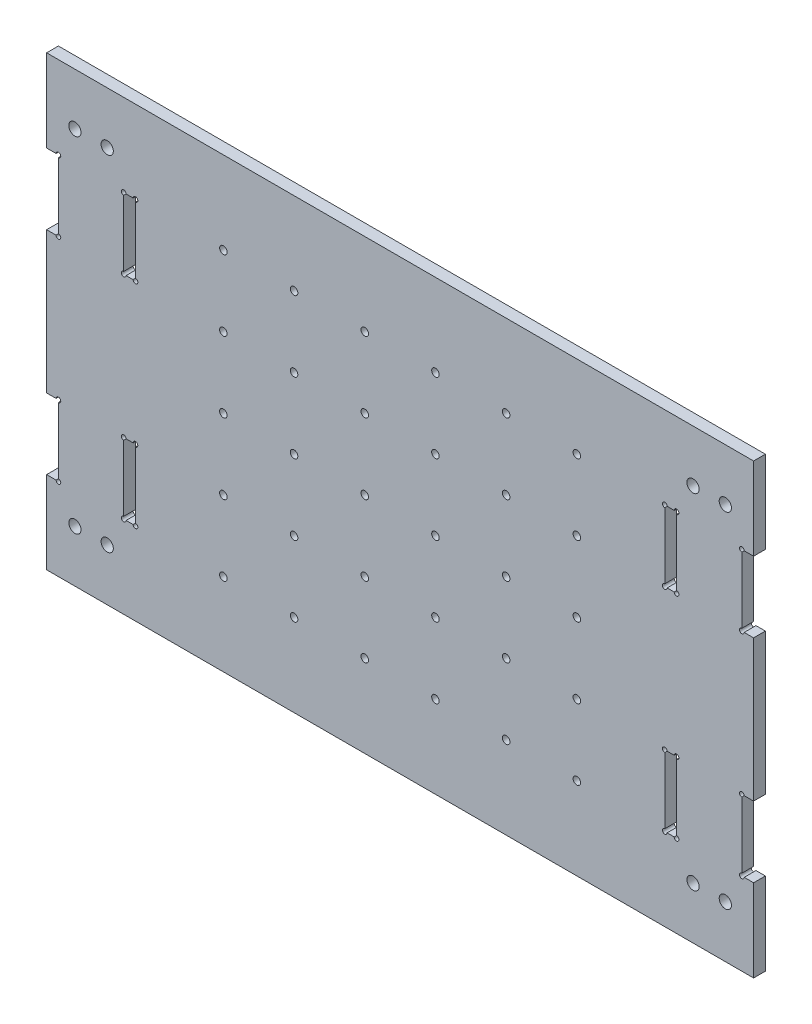
SolidWorks part; units mm, degrees
ref_plane "前视基准面" through (0, 0, 0) normal (0, 0, 1) x (1, 0, 0)
ref_plane "上视基准面" through (0, 0, 0) normal (0, 1, 0) x (1, 0, 0)
ref_plane "右视基准面" through (0, 0, 0) normal (1, 0, 0) x (0, 0, -1)
other "Configuration Table"
sketch "草图1" plane through (0, 0, 0) normal (0, 0, 1) x (1, 0, 0)
  line L0 (0, -95) -> (300, -95) construction
  line L1 (0, 0) -> (300, 0)
  line L2 (0, 0) -> (0, -190)
  line L3 (0, -190) -> (300, -190)
  line L4 (300, 0) -> (300, -190)
  line L5 (50, 0) -> (250, 0)
  line L6 (50, 0) -> (50, -50)
  line L7 (50, -50) -> (250, -50)
  line L8 (250, 0) -> (250, -50)
  line L9 (250, -190) -> (250, -140)
  line L10 (50, -140) -> (250, -140)
  line L11 (50, -190) -> (50, -140)
  dimension "D1" = 300
  dimension "D2" = 190
  dimension "D3" = 50
  dimension "D4" = 50
  dimension "D5" = 50
extrude "凸台-拉伸2" add sketch "草图1" along normal blind 5 contours L2 L0 L4 L1 L8 L7 L6 | L0 L2 L3 L11 L10 L9 L4 region at (150, -59.6622, 0) region at (150, -130.3378, 0)
sketch "草图2" plane through (0, 0, 5) normal (0, 0, 1) x (1, 0, 0)
  line L0 (0, -95) -> (300, -95) construction
  line L1 (150, -50) -> (150, -140) construction
  line L2 (0, -35) -> (5, -35)
  line L3 (0, -35) -> (0, -65)
  line L4 (0, -65) -> (5, -65)
  line L5 (5, -35) -> (5, -65)
  line L6 (0, -155) -> (5, -155)
  line L7 (5, -155) -> (5, -125)
  line L8 (0, -125) -> (5, -125)
  line L9 (300, -155) -> (295, -155)
  line L10 (295, -155) -> (295, -125)
  line L11 (300, -125) -> (295, -125)
  line L12 (0, 0) -> (0, -190)
  line L13 (0, -190) -> (50, -190)
  line L14 (50, -190) -> (50, -140)
  line L15 (50, -140) -> (250, -140)
  line L16 (250, -140) -> (250, -190)
  line L17 (250, -190) -> (300, -190)
  line L18 (300, -190) -> (300, 0)
  line L19 (300, 0) -> (250, 0)
  line L20 (250, 0) -> (250, -50)
  line L21 (250, -50) -> (50, -50)
  line L22 (50, -50) -> (50, 0)
  line L23 (50, 0) -> (0, 0)
  line L24 (0, 0) -> (0, -190)
  line L25 (0, -190) -> (50, -190)
  line L26 (50, -190) -> (50, -140)
  line L27 (50, -140) -> (250, -140)
  line L28 (250, -140) -> (250, -190)
  line L29 (250, -190) -> (300, -190)
  line L30 (300, -190) -> (300, 0)
  line L31 (300, 0) -> (250, 0)
  line L32 (250, 0) -> (250, -50)
  line L33 (250, -50) -> (50, -50)
  line L34 (50, -50) -> (50, 0)
  line L35 (50, 0) -> (0, 0)
  line L36 (300, -65) -> (295, -65)
  line L37 (300, -35) -> (295, -35)
  line L38 (295, -35) -> (295, -65)
  line M22 (0, 0) -> (0, -190)
  line M28 (300, -190) -> (300, 0)
  dimension "D2" = 30
  dimension "D3" = 30
  dimension "D4" = 5
  dimension "D1" = 0
extrude "切除-拉伸1" cut sketch "草图2" against normal blind 10 contours L5 L2 L4 M22 | L8 L6 L7 M22 | L37 L38 L36 L30 | L11 L10 L9 M28 region at (2.5, -50, 5) region at (2.5, -140, 5) region at (297.5, -50, 5) region at (297.5, -140, 5)
sketch "草图3" plane through (0, 0, 5) normal (0, 0, 1) x (1, 0, 0)
  line L0 (150, -50) -> (150, -140) construction
  line L1 (0, -95) -> (300, -95)
  line L28 (0, -65) -> (0, -125)
  line L29 (0, -125) -> (5, -125)
  line L30 (5, -125) -> (5, -155)
  line L31 (5, -155) -> (0, -155)
  line L32 (0, -155) -> (0, -190)
  line L33 (0, -190) -> (50, -190)
  line L34 (50, -190) -> (50, -140)
  line L35 (50, -140) -> (250, -140)
  line L36 (250, -140) -> (250, -190)
  line L37 (250, -190) -> (300, -190)
  line L38 (300, -190) -> (300, -155)
  line L39 (300, -155) -> (295, -155)
  line L40 (295, -155) -> (295, -125)
  line L41 (295, -125) -> (300, -125)
  line L42 (300, -125) -> (300, -65)
  line L43 (300, -65) -> (295, -65)
  line L44 (295, -65) -> (295, -35)
  line L45 (295, -35) -> (300, -35)
  line L46 (300, -35) -> (300, 0)
  line L47 (300, 0) -> (250, 0)
  line L48 (250, 0) -> (250, -50)
  line L49 (250, -50) -> (50, -50)
  line L50 (50, -50) -> (50, 0)
  line L51 (50, 0) -> (0, 0)
  line L52 (0, 0) -> (0, -35)
  line L53 (0, -35) -> (5, -35)
  line L54 (5, -35) -> (5, -65)
  line L55 (5, -65) -> (0, -65)
  line L56 (0, -65) -> (0, -125)
  line L57 (0, -125) -> (5, -125)
  line L58 (5, -125) -> (5, -155)
  line L59 (5, -155) -> (0, -155)
  line L60 (0, -155) -> (0, -190)
  line L61 (0, -190) -> (50, -190)
  line L62 (50, -190) -> (50, -140)
  line L63 (50, -140) -> (250, -140)
  line L64 (250, -140) -> (250, -190)
  line L65 (250, -190) -> (300, -190)
  line L66 (300, -190) -> (300, -155)
  line L67 (300, -155) -> (295, -155)
  line L68 (295, -155) -> (295, -125)
  line L69 (295, -125) -> (300, -125)
  line L70 (300, -125) -> (300, -65)
  line L71 (300, -65) -> (295, -65)
  line L72 (295, -65) -> (295, -35)
  line L73 (295, -35) -> (300, -35)
  line L74 (300, -35) -> (300, 0)
  line L75 (300, 0) -> (250, 0)
  line L76 (250, 0) -> (250, -50)
  line L77 (250, -50) -> (50, -50)
  line L78 (50, -50) -> (50, 0)
  line L79 (50, 0) -> (0, 0)
  line L80 (0, 0) -> (0, -35)
  line L81 (0, -35) -> (5, -35)
  line L82 (5, -35) -> (5, -65)
  line L83 (5, -65) -> (0, -65)
  circle A0 centre (5, -35) radius 1
  circle A1 centre (5, -65) radius 1
  circle A2 centre (5, -125) radius 1
  circle A3 centre (5, -155) radius 1
  circle A4 centre (295, -35) radius 1
  circle A5 centre (295, -65) radius 1
  circle A6 centre (295, -125) radius 1
  circle A7 centre (295, -155) radius 1
  line M31 (5, -125) -> (5, -155)
  line M32 (5, -155) -> (0, -155)
  line M41 (295, -155) -> (295, -125)
  line M42 (295, -125) -> (300, -125)
  line M45 (295, -65) -> (295, -35)
  line M46 (295, -35) -> (300, -35)
  line M55 (5, -35) -> (5, -65)
  line M56 (5, -65) -> (0, -65)
  dimension "D2" = 2
  dimension "D3" = 2
  dimension "D1" = 0
extrude "切除-拉伸2" cut sketch "草图3" against normal blind 10 contours A0 L81 M55 | L81 A0 M55 | A1 M56 M55 | A2 L57 M31 | A3 M31 M32 | A7 L67 M41 | A6 L68 M42 | A4 L72 M46 | A5 L71 M45 region at (5.1415, -65.1415, 5) region at (5.1415, -124.8585, 5) region at (294.8585, -124.8585, 5) region at (294.8585, -65.1415, 5) region at (4.5756, -35.4244, 5) region at (5.1415, -34.8585, 5) region at (5.1415, -155.1415, 5) region at (294.8585, -155.1415, 5) region at (294.8585, -34.8585, 5)
sketch "草图4" plane through (50, 0, 0) normal (1, 0, 0) x (0, 0, -1)
  line L4 (0, -50) -> (0, 0)
  line L5 (0, 0) -> (-5, 0)
  line L6 (-5, 0) -> (-5, -50)
  line L7 (-5, -50) -> (0, -50)
  line L8 (0, -50) -> (0, 0)
  line L9 (0, 0) -> (-5, 0)
  line L10 (-5, 0) -> (-5, -50)
  line L11 (-5, -50) -> (0, -50)
  line L12 (0, -190) -> (0, -140)
  line L13 (0, -140) -> (-5, -140)
  line L14 (-5, -140) -> (-5, -190)
  line L15 (-5, -190) -> (0, -190)
  line L16 (0, -190) -> (0, -140)
  line L17 (0, -140) -> (-5, -140)
  line L18 (-5, -140) -> (-5, -190)
  line L19 (-5, -190) -> (0, -190)
  dimension "D1" = 0
  dimension "D2" = 0
extrude "凸台-拉伸3" add sketch "草图4" along normal up to next
sketch "草图5" plane through (0, 0, 5) normal (0, 0, 1) x (1, 0, 0)
  line L0 (150, 0) -> (150, -190)
  line L1 (32.7, -35) -> (37.7, -35)
  line L2 (32.7, -35) -> (32.7, -65)
  line L3 (32.7, -65) -> (37.7, -65)
  line L4 (37.7, -35) -> (37.7, -65)
  line L5 (0, -95) -> (300, -95)
  line L6 (32.7, -125) -> (37.7, -125)
  line L7 (37.7, -155) -> (37.7, -125)
  line L8 (32.7, -155) -> (37.7, -155)
  line L9 (32.7, -155) -> (32.7, -125)
  line L10 (267.3, -155) -> (267.3, -125)
  line L11 (267.3, -155) -> (262.3, -155)
  line L12 (262.3, -155) -> (262.3, -125)
  line L13 (267.3, -125) -> (262.3, -125)
  line L14 (267.3, -65) -> (262.3, -65)
  line L15 (262.3, -35) -> (262.3, -65)
  line L16 (267.3, -35) -> (262.3, -35)
  line L17 (267.3, -35) -> (267.3, -65)
  line L20 (300, 0) -> (0, 0)
  line L21 (0, 0) -> (0, -35)
  line L22 (0, -35) -> (4, -35)
  line L23 (5, -36) -> (5, -64)
  line L24 (4, -65) -> (0, -65)
  line L25 (0, -65) -> (0, -125)
  line L26 (0, -125) -> (4, -125)
  line L27 (5, -126) -> (5, -154)
  line L28 (4, -155) -> (0, -155)
  line L29 (0, -155) -> (0, -190)
  line L30 (0, -190) -> (300, -190)
  line L31 (300, -190) -> (300, -155)
  line L32 (300, -155) -> (296, -155)
  line L33 (295, -154) -> (295, -126)
  line L34 (296, -125) -> (300, -125)
  line L35 (300, -125) -> (300, -65)
  line L36 (300, -65) -> (296, -65)
  line L37 (295, -64) -> (295, -36)
  line L38 (296, -35) -> (300, -35)
  line L39 (300, -35) -> (300, 0)
  line L40 (300, 0) -> (0, 0)
  line L41 (0, 0) -> (0, -35)
  line L42 (0, -35) -> (4, -35)
  line L43 (5, -36) -> (5, -64)
  line L44 (4, -65) -> (0, -65)
  line L45 (0, -65) -> (0, -125)
  line L46 (0, -125) -> (4, -125)
  line L47 (5, -126) -> (5, -154)
  line L48 (4, -155) -> (0, -155)
  line L49 (0, -155) -> (0, -190)
  line L50 (0, -190) -> (300, -190)
  line L51 (300, -190) -> (300, -155)
  line L52 (300, -155) -> (296, -155)
  line L53 (295, -154) -> (295, -126)
  line L54 (296, -125) -> (300, -125)
  line L55 (300, -125) -> (300, -65)
  line L56 (300, -65) -> (296, -65)
  line L57 (295, -64) -> (295, -36)
  line L58 (296, -35) -> (300, -35)
  line L59 (300, -35) -> (300, 0)
  circle A0 centre (32.7, -35) radius 1
  circle A1 centre (37.7, -35) radius 1
  circle A2 centre (32.7, -65) radius 1
  circle A3 centre (37.7, -65) radius 1
  circle A4 centre (37.7, -125) radius 1
  circle A5 centre (32.7, -125) radius 1
  circle A6 centre (37.7, -155) radius 1
  circle A7 centre (32.7, -155) radius 1
  arc A8 (5, -36) -> (4, -35) centre (5, -35) ccw
  arc A9 (4, -65) -> (5, -64) centre (5, -65) ccw
  arc A10 (5, -126) -> (4, -125) centre (5, -125) ccw
  arc A11 (4, -155) -> (5, -154) centre (5, -155) ccw
  arc A12 (295, -154) -> (296, -155) centre (295, -155) ccw
  arc A13 (296, -125) -> (295, -126) centre (295, -125) ccw
  arc A14 (295, -64) -> (296, -65) centre (295, -65) ccw
  arc A15 (296, -35) -> (295, -36) centre (295, -35) ccw
  arc A16 (5, -36) -> (4, -35) centre (5, -35) ccw
  arc A17 (4, -65) -> (5, -64) centre (5, -65) ccw
  arc A18 (5, -126) -> (4, -125) centre (5, -125) ccw
  arc A19 (4, -155) -> (5, -154) centre (5, -155) ccw
  arc A20 (295, -154) -> (296, -155) centre (295, -155) ccw
  arc A21 (296, -125) -> (295, -126) centre (295, -125) ccw
  arc A22 (295, -64) -> (296, -65) centre (295, -65) ccw
  arc A23 (296, -35) -> (295, -36) centre (295, -35) ccw
  circle A24 centre (262.3, -155) radius 1
  circle A25 centre (267.3, -155) radius 1
  circle A26 centre (262.3, -125) radius 1
  circle A27 centre (267.3, -125) radius 1
  circle A28 centre (262.3, -35) radius 1
  circle A29 centre (267.3, -35) radius 1
  circle A30 centre (267.3, -65) radius 1
  circle A31 centre (262.3, -65) radius 1
  dimension "D4" = 2
  dimension "D5" = 2
  dimension "D6" = 2
  dimension "D7" = 2
  dimension "D2" = 32.7
  dimension "D3" = 5
  dimension "D1" = 0
extrude "切除-拉伸3" cut sketch "草图5" against normal blind 5 contours A3 L4 A1 L1 A0 L2 A2 L3 | L1 A0 L2 | L4 A1 L1 | L1 A1 L4 | L2 A0 L1 | L3 A2 L2 | L2 A2 L3 | L3 A3 L4 | L4 A3 L3 | A7 L8 L9 | A7 L9 L8 | L9 A7 L8 A6 L7 A4 L6 A5 | A6 L8 L7 | A6 L7 L8 | A5 L9 L6 | A5 L6 L9 | A4 L6 L7 | A4 L7 L6 | L15 A31 L14 A30 L17 A29 L16 A28 | A28 L15 L16 | A28 L16 L15 | A29 L17 L16 | A29 L16 L17 | A31 L15 L14 | A31 L14 L15 | A30 L17 L14 | A30 L14 L17 | L13 A26 L12 | L12 A26 L13 | A27 L13 A26 L12 A24 L11 A25 L10 | L13 A27 L10 | L10 A27 L13 | L12 A24 L11 | L11 A24 L12 | L11 A25 L10 | L10 A25 L11 region at (32.5585, -34.8585, 5) region at (33.1244, -35.4244, 5) region at (35.2, -50, 5) region at (37.8415, -34.8585, 5) region at (37.2756, -35.4244, 5) region at (33.1244, -64.5756, 5) region at (32.5585, -65.1415, 5) region at (37.8415, -65.1415, 5) region at (37.2756, -64.5756, 5) region at (32.5585, -124.8585, 5) region at (33.1244, -125.4244, 5) region at (35.2, -140, 5) region at (37.8415, -124.8585, 5) region at (37.2756, -125.4244, 5) region at (33.1244, -154.5756, 5) region at (32.5585, -155.1415, 5) region at (37.8415, -155.1415, 5) region at (37.2756, -154.5756, 5) region at (266.8756, -154.5756, 5) region at (267.4415, -155.1415, 5) region at (264.8, -140, 5) region at (266.8756, -125.4244, 5) region at (267.4415, -124.8585, 5) region at (262.1585, -155.1415, 5) region at (262.7244, -154.5756, 5) region at (262.7244, -125.4244, 5) region at (262.1585, -124.8585, 5) region at (262.1585, -65.1415, 5) region at (264.8, -50, 5) region at (262.7244, -64.5756, 5) region at (266.8756, -64.5756, 5) region at (267.4415, -65.1415, 5) region at (262.1585, -34.8585, 5) region at (262.7244, -35.4244, 5) region at (266.8756, -35.4244, 5) region at (267.4415, -34.8585, 5)
sketch "草图6" plane through (0, 0, 5) normal (0, 0, 1) x (1, 0, 0)
  line L0 (4, -160) -> (127.3647, -160)
  line L1 (32.7, -154) -> (32.7, -126) construction
  line L2 (0, -95) -> (300, -95)
  line L3 (150, 0) -> (150, -190)
  line L20 (300, 0) -> (0, 0)
  line L21 (0, 0) -> (0, -35)
  line L22 (0, -35) -> (4, -35)
  line L23 (5, -36) -> (5, -64)
  line L24 (4, -65) -> (0, -65)
  line L25 (0, -65) -> (0, -125)
  line L26 (0, -125) -> (4, -125)
  line L27 (5, -126) -> (5, -154)
  line L28 (4, -155) -> (0, -155)
  line L29 (0, -155) -> (0, -190)
  line L30 (0, -190) -> (300, -190)
  line L31 (300, -190) -> (300, -155)
  line L32 (300, -155) -> (296, -155)
  line L33 (295, -154) -> (295, -126)
  line L34 (296, -125) -> (300, -125)
  line L35 (300, -125) -> (300, -65)
  line L36 (300, -65) -> (296, -65)
  line L37 (295, -64) -> (295, -36)
  line L38 (296, -35) -> (300, -35)
  line L39 (300, -35) -> (300, 0)
  line L40 (300, 0) -> (0, 0)
  line L41 (0, 0) -> (0, -35)
  line L42 (0, -35) -> (4, -35)
  line L43 (5, -36) -> (5, -64)
  line L44 (4, -65) -> (0, -65)
  line L45 (0, -65) -> (0, -125)
  line L46 (0, -125) -> (4, -125)
  line L47 (5, -126) -> (5, -154)
  line L48 (4, -155) -> (0, -155)
  line L49 (0, -155) -> (0, -190)
  line L50 (0, -190) -> (300, -190)
  line L51 (300, -190) -> (300, -155)
  line L52 (300, -155) -> (296, -155)
  line L53 (295, -154) -> (295, -126)
  line L54 (296, -125) -> (300, -125)
  line L55 (300, -125) -> (300, -65)
  line L56 (300, -65) -> (296, -65)
  line L57 (295, -64) -> (295, -36)
  line L58 (296, -35) -> (300, -35)
  line L59 (300, -35) -> (300, 0)
  circle A0 centre (12, -168) radius 2.6
  circle A1 centre (25.7, -168) radius 2.6
  circle A2 centre (25.7, -22) radius 2.6
  circle A3 centre (12, -22) radius 2.6
  circle A4 centre (274.3, -168) radius 2.6
  circle A5 centre (288, -168) radius 2.6
  circle A6 centre (274.3, -22) radius 2.6
  circle A7 centre (288, -22) radius 2.6
  arc A8 (5, -36) -> (4, -35) centre (5, -35) ccw
  arc A9 (4, -65) -> (5, -64) centre (5, -65) ccw
  arc A10 (5, -126) -> (4, -125) centre (5, -125) ccw
  arc A11 (4, -155) -> (5, -154) centre (5, -155) ccw
  arc A12 (295, -154) -> (296, -155) centre (295, -155) ccw
  arc A13 (296, -125) -> (295, -126) centre (295, -125) ccw
  arc A14 (295, -64) -> (296, -65) centre (295, -65) ccw
  arc A15 (296, -35) -> (295, -36) centre (295, -35) ccw
  arc A16 (5, -36) -> (4, -35) centre (5, -35) ccw
  arc A17 (4, -65) -> (5, -64) centre (5, -65) ccw
  arc A18 (5, -126) -> (4, -125) centre (5, -125) ccw
  arc A19 (4, -155) -> (5, -154) centre (5, -155) ccw
  arc A20 (295, -154) -> (296, -155) centre (295, -155) ccw
  arc A21 (296, -125) -> (295, -126) centre (295, -125) ccw
  arc A22 (295, -64) -> (296, -65) centre (295, -65) ccw
  arc A23 (296, -35) -> (295, -36) centre (295, -35) ccw
  dimension "D3" = 5.2
  dimension "D4" = 5.2
  dimension "D5" = 8
  dimension "D2" = 30
  dimension "D6" = 7
  dimension "D7" = 8
  dimension "D8" = 7
  dimension "D1" = 0
extrude "切除-拉伸4" cut sketch "草图6" against normal through all contours A3 | A2 | A0 | A1 | A4 | A5 | A6 | A7 region at (12, -168, 5) region at (25.7, -168, 5) region at (25.7, -22, 5) region at (12, -22, 5) region at (274.3, -168, 5) region at (288, -168, 5) region at (274.3, -22, 5) region at (288, -22, 5)
sketch "草图7" plane through (0, 0, 5) normal (0, 0, 1) x (1, 0, 0)
  line L1 (0, 0) -> (300, 0) construction
  line L6 (300, 0) -> (300, -35) construction
  circle A0 centre (75, -35) radius 1.6
  circle A1 centre (105, -35) radius 1.6
  circle A2 centre (135, -35) radius 1.6
  circle A3 centre (165, -35) radius 1.6
  circle A4 centre (195, -35) radius 1.6
  circle A5 centre (225, -35) radius 1.6
  circle A6 centre (105, -65) radius 1.6
  circle A7 centre (135, -65) radius 1.6
  circle A8 centre (165, -65) radius 1.6
  circle A9 centre (195, -65) radius 1.6
  circle A10 centre (225, -65) radius 1.6
  circle A11 centre (105, -95) radius 1.6
  circle A12 centre (135, -95) radius 1.6
  circle A13 centre (165, -95) radius 1.6
  circle A14 centre (195, -95) radius 1.6
  circle A15 centre (225, -95) radius 1.6
  circle A16 centre (105, -125) radius 1.6
  circle A17 centre (135, -125) radius 1.6
  circle A18 centre (165, -125) radius 1.6
  circle A19 centre (195, -125) radius 1.6
  circle A20 centre (225, -125) radius 1.6
  circle A21 centre (105, -155) radius 1.6
  circle A22 centre (135, -155) radius 1.6
  circle A23 centre (165, -155) radius 1.6
  circle A24 centre (195, -155) radius 1.6
  circle A25 centre (225, -155) radius 1.6
  circle A26 centre (75, -65) radius 1.6
  circle A27 centre (75, -95) radius 1.6
  circle A28 centre (75, -125) radius 1.6
  circle A29 centre (75, -155) radius 1.6
  dimension "D1" = 3.2
  dimension "D2" = 35
  dimension "D5" = 75
  dimension "D3" = 6
  dimension "D4" = 5
extrude "切除-拉伸5" cut sketch "草图7" against normal through all
